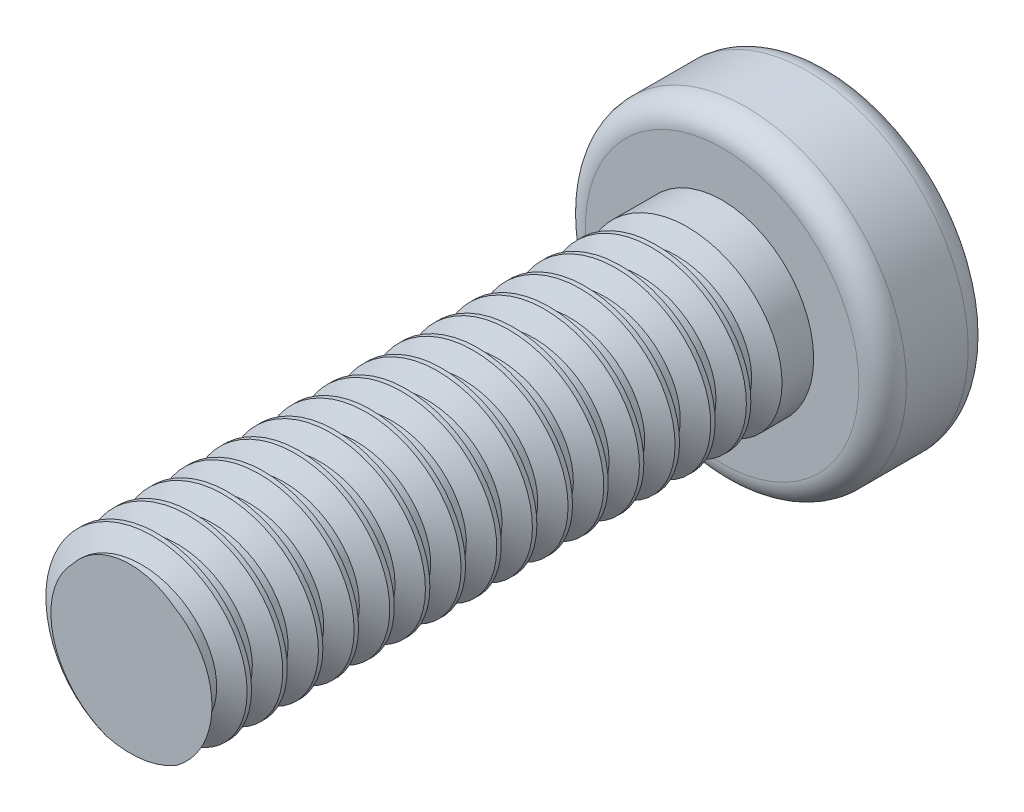
SolidWorks part; units mm, degrees
ref_plane "Front Plane" through (0, 0, 0) normal (0, 0, 1) x (1, 0, 0)
ref_plane "Top Plane" through (0, 0, 0) normal (0, 1, 0) x (1, 0, 0)
ref_plane "Right Plane" through (0, 0, 0) normal (1, 0, 0) x (0, 0, -1)
sketch "Sketch1" plane through (0, 0, 0) normal (0, 0, 1) x (1, 0, 0)
  line L1 (7.0092, -3.409) -> (6.4569, 4.3656)
  line L2 (6.4569, 4.3656) -> (-0.5523, 7.7746)
  line L3 (-0.5523, 7.7746) -> (-7.0092, 3.409)
  line L4 (-7.0092, 3.409) -> (-6.4569, -4.3656)
  line L5 (-6.4569, -4.3656) -> (0.5523, -7.7746)
  line L6 (0.5523, -7.7746) -> (7.0092, -3.409)
  circle A0 centre (0, 0) radius 6.75 construction
  dimension "D1" = 13.5
extrude "Boss-Extrude1" add sketch "Sketch1" along normal blind 4.6 contours L3 L4 L5 L6 L1 L2
sketch "Sketch3" plane through (0, 0, 4.6) normal (0, 0, 1) x (1, 0, 0)
  circle A0 centre (0, 0) radius 3.85
  dimension "D1" = 7.7
extrude "Boss-Extrude2" add sketch "Sketch3" along normal blind 24.9
sketch "Sketch4" plane through (0, 0, 4.6) normal (0, 0, 1) x (1, 0, 0)
  circle A0 centre (0, 0) radius 6.75
extrude "Cut-Extrude3" cut sketch "Sketch4" against normal blind 24.9 flip side to cut
sketch "Sketch13" plane through (0, 0, 0) normal (0, 0, -1) x (-1, 0, 0)
  line L0 (0, 0) -> (1.5982, 2.3597)
  line L2 (1.5982, 2.3597) -> (-1.2444, 2.564)
  line L3 (-1.2444, 2.564) -> (-2.8427, 0.2043)
  line L4 (-2.8427, 0.2043) -> (-1.5982, -2.3597)
  line L5 (-1.5982, -2.3597) -> (1.2444, -2.564)
  line L6 (1.2444, -2.564) -> (2.8427, -0.2043)
  line L7 (2.8427, -0.2043) -> (1.5982, 2.3597)
  circle A0 centre (0, 0) radius 2.4682 construction
  dimension "D1" = 2.85
extrude "Cut-Extrude4" cut sketch "Sketch13" against normal blind 3.5 contours L2 L3 L4 L5 L6 L7
fillet "Fillet8" radius 1 2 edges at (6.75, 0, 0) (6.75, 0, 4.6)
thread "Thread8" pitch 1.5 start angle 0, offset 23, length 33, pitch 1.5, diameter 7.7
ref_plane "Plane8" through (-3.85, 0, 6.5) normal (0, -1, 0) x (-1, 0, 0)
sketch "Thread Profile8" plane through (-3.85, 0, 6.5) normal (0, -1, 0) x (-1, 0, 0)
  line L0 (0, 0) -> (0, 1.5) construction
  line L11 (0, 0) -> (0, 1.3125)
  line L12 (0, 1.3125) -> (-0.8119, 0.8437)
  line L13 (-0.8119, 0.8437) -> (-0.8119, 0.4687)
  line L15 (-0.8119, 0.4687) -> (0, 0)
  line L17 (-0.8119, 0.6562) -> (0, 0.6562) construction
  point P2 (0, 0)
  dimension "Pitch" = 1.5
  dimension "Profile_Angle" = 60
  dimension "Profile_Land" = 0.375
  dimension "Profile_Height" = 0.8119
sketch "Sketch44" plane through (0, 0, 4.6) normal (0, 0, 1) x (1, 0, 0)
  circle A0 centre (0, 0) radius 3.85
  dimension "D1" = 7.7
